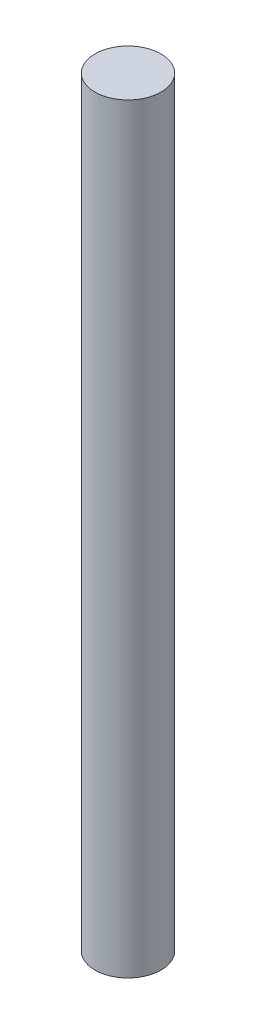
SolidWorks part; units mm, degrees
ref_plane "Front Plane" through (0, 0, 0) normal (0, 0, 1) x (1, 0, 0)
ref_plane "Top Plane" through (0, 0, 0) normal (0, 1, 0) x (1, 0, 0)
ref_plane "Right Plane" through (0, 0, 0) normal (1, 0, 0) x (0, 0, -1)
sketch "Sketch1" plane through (0, 0, 0) normal (0, 1, 0) x (1, 0, 0)
  circle A0 centre (0, 0) radius 5
  dimension "D1" = 10
extrude "Boss-Extrude1" add sketch "Sketch1" along normal blind 115
cosmetic thread "Cosmetic Thread1"
cosmetic thread "Cosmetic Thread2"
ref_axis "Axis1" through (0, 129.2291, 0) along (0, -1, 0)
